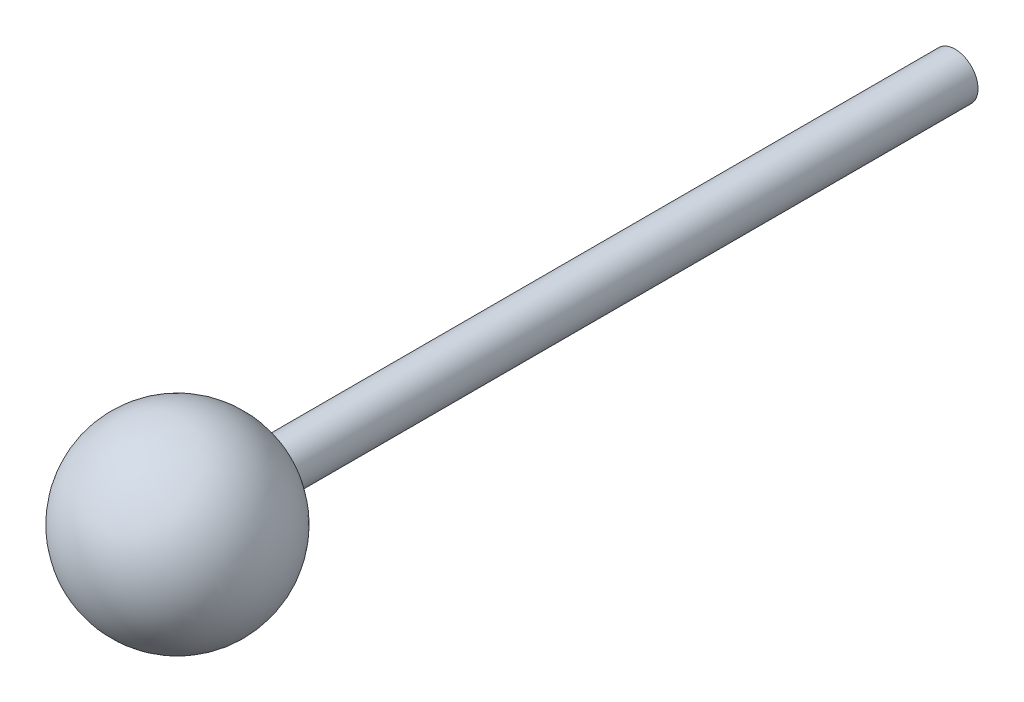
SolidWorks part; units mm, degrees
ref_plane "Front Plane" through (0, 0, 0) normal (0, 0, 1) x (1, 0, 0)
ref_plane "Top Plane" through (0, 0, 0) normal (0, 1, 0) x (1, 0, 0)
ref_plane "Right Plane" through (0, 0, 0) normal (1, 0, 0) x (0, 0, -1)
sketch "Sketch1" plane through (0, 0, 0) normal (0, 0, 1) x (1, 0, 0)
  circle A0 centre (67.9041, 47.8092) radius 0.5
extrude "Boss-Extrude1" add sketch "Sketch1" along normal blind 15
dome "Dome1" faces to dome 1 distance 4 reverse direction no elliptical dome no face at (68.4041, 47.8092, 15) parameters "D1"=4
